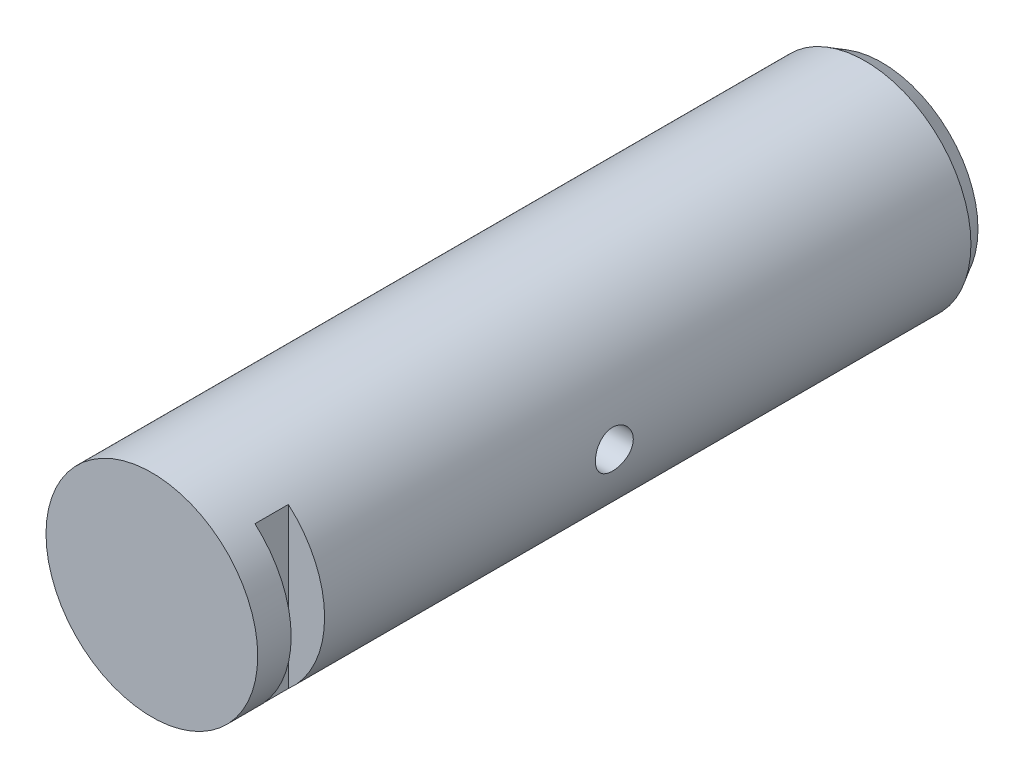
SolidWorks part; units mm, degrees
note: '?' marks a value the reader was unsure of.
material "1.7225 (42CrMo4)"
ref_plane "E_Rechts" through (0, 0, 0) normal (0, 0, 1) x (1, 0, 0)
ref_plane "E_Oben" through (0, 0, 0) normal (0, 1, 0) x (1, 0, 0)
ref_plane "E_Vorne" through (0, 0, 0) normal (1, 0, 0) x (0, 0, -1)
ref_axis "E_Drehachse" through (0, 0, 61.5) along (0, 0, -1)?
sketch "Skizze1" plane through (0, 0, 0) normal (0, 0, 1) x (1, 0, 0)
  circle A0 centre (0, 0) radius 19
  dimension "D1" = 38
extrude "Aufsatz-Linear austragen1" add sketch "Skizze1" along normal blind 75 and the other way blind 56
sketch "Skizze2" plane through (0, 0, 0) normal (1, 0, 0) x (0, 0, -1)
  line L1 (56, 19) -> (-75, 19) construction
  line L6 (-69, 19) -> (-63, 19)
  line L7 (-69, 19) -> (-69, 12.5)
  line L8 (-69, 12.5) -> (-63, 12.5)
  line L9 (-63, 19) -> (-63, 12.5)
  line L11 (0, 20.9) -> (0, -20.9) construction
  dimension "D1" = 6.5
  dimension "D2" = 6
  dimension "D3" = 63
hole_wizard "M8 Tapped Hole1" positions "Skizze3" profile "Skizze4" tap size "M8" standard "DIN"
sketch "Skizze3" plane through (0, 0, -56) normal (0, 0, -1) x (-1, 0, 0)
  point P0 (0, 0)
cosmetic thread "Bohrungsgewinde1" parameters "D1"=16, "D2"=8
sketch "Skizze4" plane through (0, 0, -56) normal (1, 0, 0) x (0, 1, 0)
  line L0 (0, 0) -> (0, 77.0429)
  line L1 (0, 77.0429) -> (3.4, 75)
  line L2 (3.4, 75) -> (3.4, 0)
  line L5 (3.4, 0) -> (0, 0)
  line L10 (0, 77.0429) -> (-3.4, 75) construction
  line L11 (0, -6.35) -> (0, 107.95) construction
  dimension "Bohrerdurchmesser" = 6.8
  dimension "Bohrungstiefe" = 75
  dimension "Spitzenwinkel" = 118
hole_wizard "Tap Drill for M8 Tap1" positions "Skizze5" profile "Skizze7" hole size "M8" standard "DIN" end condition through all
sketch "Skizze5" plane through (0, 0, 0) normal (1, 0, 0) x (0, 0, -1)
  line L0 (56, -19) -> (56, 19) construction
  point P3 (-11, 0)
  dimension "D1" = 67
sketch "Skizze7" plane through (0, 0, 11) normal (0, 1, 0) x (0, 0, 1)
  line L0 (0, 0) -> (0, 19)
  line L1 (0, 19) -> (3.4, 19)
  line L2 (3.4, 19) -> (3.4, 0)
  line L5 (3.4, 0) -> (0, 0)
  line L11 (0, -6.35) -> (0, 107.95) construction
  dimension "Bohrerdurchmesser" = 6.8
  dimension "Bohrungstiefe" = 19
mirror "Spiegeln1" about plane through (0, 0, 0) normal (1, 0, 0) of "Tap Drill for M8 Tap1"
chamfer "Chamfer1" distance 3 angle 30 1 edges at (19, 0, -56) first distance on face at (-18.9863, 0.7213, 14.3226)
sketch "Sketch2" plane through (0, 0, 0) normal (0, 1, 0) x (1, 0, 0)
  line L0 (19, -75) -> (19, -14.4) construction
  line L1 (19, -63) -> (12.5, -63)
  line L2 (19, -63) -> (19, -69)
  line L3 (19, -69) -> (12.5, -69)
  line L4 (12.5, -63) -> (12.5, -69)
  line L5 (-19, -75) -> (19, -75) construction
  dimension "D1" = 12
  dimension "D2" = 6
  dimension "D3" = 6.5
extrude "Cut-Extrude2" cut sketch "Sketch2" against normal through all both and the other way through all
